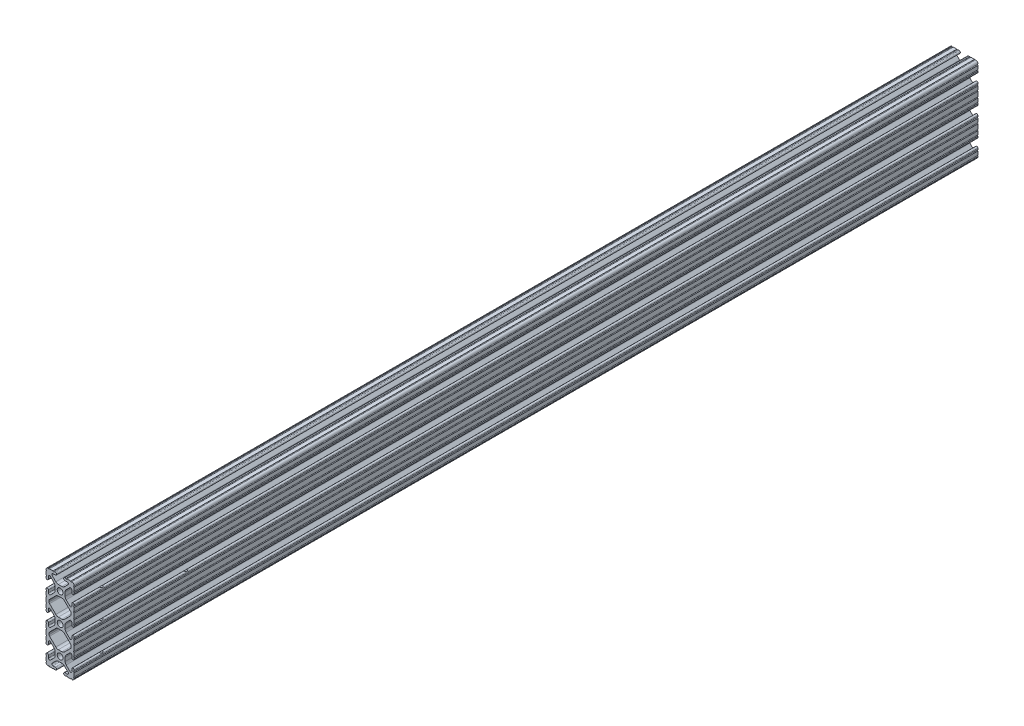
SolidWorks part; units mm, degrees
ref_plane "Front" through (0, 0, 0) normal (0, 0, 1) x (1, 0, 0)
ref_plane "Top" through (0, 0, 0) normal (0, 1, 0) x (1, 0, 0)
ref_plane "Right" through (0, 0, 0) normal (1, 0, 0) x (0, 0, -1)
sketch "Sketch1" plane through (0, 0, 0) normal (0, 0, 1) x (1, 0, 0)
  line L0 (-7.4908, -34.8742) -> (7.4908, -34.8742) construction
  line L1 (-3.1974, -36.9951) -> (3.1974, -36.9951) construction
  line L2 (-7.4908, 34.8742) -> (7.4908, 34.8742) construction
  line L3 (-3.1974, 36.9951) -> (3.1974, 36.9951) construction
  line L16 (-9.9314, -12.1463) -> (-9.9314, -13.2537)
  line L17 (-3.8759, -5.4384) -> (-9.4702, -11.0327)
  line L18 (1.6308, -4.5085) -> (-1.6308, -4.5085)
  line L19 (9.4702, -11.0327) -> (3.8759, -5.4384)
  line L20 (9.9314, -13.2537) -> (9.9314, -12.1463)
  line L21 (3.8759, -19.9616) -> (9.4702, -14.3673)
  line L22 (-1.6308, -20.8915) -> (1.6308, -20.8915)
  line L23 (-9.4702, -14.3673) -> (-3.8759, -19.9616)
  line L32 (-9.9314, 13.2537) -> (-9.9314, 12.1463)
  line L33 (-3.8759, 19.9616) -> (-9.4702, 14.3673)
  line L34 (1.6308, 20.8915) -> (-1.6308, 20.8915)
  line L35 (9.4702, 14.3673) -> (3.8759, 19.9616)
  line L36 (9.9314, 12.1463) -> (9.9314, 13.2537)
  line L37 (3.8759, 5.4384) -> (9.4702, 11.0327)
  line L38 (-1.6308, 4.5085) -> (1.6308, 4.5085)
  line L39 (-9.4702, 11.0327) -> (-3.8759, 5.4384)
  line L152 (-12.7, 34.9504) -> (-12.7, 31.7246)
  line L153 (-12.7, 30.7086) -> (-12.7, 29.7023)
  line L154 (-10.4902, 29.7023) -> (-10.4902, 31.8748)
  line L155 (-8.7558, 32.5932) -> (-5.4384, 29.2759)
  line L156 (-4.5085, 27.0308) -> (-4.5085, 23.7692)
  line L157 (-5.4384, 21.5241) -> (-8.7558, 18.2068)
  line L158 (-10.4902, 18.9252) -> (-10.4902, 21.0977)
  line L159 (-12.7, 21.0977) -> (-12.7, 20.0914)
  line L160 (-12.7, 19.0754) -> (-12.7, 15.8496)
  line L161 (-12.7, 14.8336) -> (-12.7, 10.5664)
  line L162 (-12.7, 9.5504) -> (-12.7, 6.3246)
  line L163 (-12.7, 5.3086) -> (-12.7, 4.3023)
  line L164 (-10.4902, 4.3023) -> (-10.4902, 6.4748)
  line L165 (-8.7558, 7.1932) -> (-5.4384, 3.8759)
  line L166 (-4.5085, 1.6308) -> (-4.5085, -1.6308)
  line L167 (-5.4384, -3.8759) -> (-8.7558, -7.1932)
  line L168 (-10.4902, -6.4748) -> (-10.4902, -4.3023)
  line L169 (-12.7, -4.3023) -> (-12.7, -5.3086)
  line L170 (-12.7, -6.3246) -> (-12.7, -9.5504)
  line L171 (-12.7, -10.5664) -> (-12.7, -14.8336)
  line L172 (-12.7, -15.8496) -> (-12.7, -19.0754)
  line L173 (-12.7, -20.0914) -> (-12.7, -21.0977)
  line L174 (-10.4902, -21.0977) -> (-10.4902, -18.9252)
  line L175 (-8.7558, -18.2068) -> (-5.4384, -21.5241)
  line L176 (-4.5085, -23.7692) -> (-4.5085, -27.0308)
  line L177 (-5.4384, -29.2759) -> (-8.7558, -32.5932)
  line L178 (-10.4902, -31.8748) -> (-10.4902, -29.7023)
  line L179 (-12.7, -29.7023) -> (-12.7, -30.7086)
  line L180 (-12.7, -31.7246) -> (-12.7, -34.9504)
  line L181 (-9.5504, -38.1) -> (-6.3246, -38.1)
  line L182 (-5.3086, -38.1) -> (-4.3023, -38.1)
  line L183 (-4.3023, -35.8902) -> (-6.4748, -35.8902)
  line L184 (-7.1932, -34.1558) -> (-3.8759, -30.8384)
  line L185 (-1.6308, -29.9085) -> (1.6308, -29.9085)
  line L186 (3.8759, -30.8384) -> (7.1932, -34.1558)
  line L187 (6.4748, -35.8902) -> (4.3023, -35.8902)
  line L188 (4.3023, -38.1) -> (5.3086, -38.1)
  line L189 (6.3246, -38.1) -> (9.5504, -38.1)
  line L190 (12.7, -34.9504) -> (12.7, -31.7246)
  line L191 (12.7, -30.7086) -> (12.7, -29.7023)
  line L192 (10.4902, -29.7023) -> (10.4902, -31.8748)
  line L193 (8.7558, -32.5932) -> (5.4384, -29.2759)
  line L194 (4.5085, -27.0308) -> (4.5085, -23.7692)
  line L195 (5.4384, -21.5241) -> (8.7558, -18.2068)
  line L196 (10.4902, -18.9252) -> (10.4902, -21.0977)
  line L197 (12.7, -21.0977) -> (12.7, -20.0914)
  line L198 (12.7, -19.0754) -> (12.7, -15.8496)
  line L199 (12.7, -14.8336) -> (12.7, -10.5664)
  line L200 (12.7, -9.5504) -> (12.7, -6.3246)
  line L201 (12.7, -5.3086) -> (12.7, -4.3023)
  line L202 (10.4902, -4.3023) -> (10.4902, -6.4748)
  line L203 (8.7558, -7.1932) -> (5.4384, -3.8759)
  line L204 (4.5085, -1.6308) -> (4.5085, 1.6308)
  line L205 (5.4384, 3.8759) -> (8.7558, 7.1932)
  line L206 (10.4902, 6.4748) -> (10.4902, 4.3023)
  line L207 (12.7, 4.3023) -> (12.7, 5.3086)
  line L208 (12.7, 6.3246) -> (12.7, 9.5504)
  line L209 (12.7, 10.5664) -> (12.7, 14.8336)
  line L210 (12.7, 15.8496) -> (12.7, 19.0754)
  line L211 (12.7, 20.0914) -> (12.7, 21.0977)
  line L212 (10.4902, 21.0977) -> (10.4902, 18.9252)
  line L213 (8.7558, 18.2068) -> (5.4384, 21.5241)
  line L214 (4.5085, 23.7692) -> (4.5085, 27.0308)
  line L215 (5.4384, 29.2759) -> (8.7558, 32.5932)
  line L216 (10.4902, 31.8748) -> (10.4902, 29.7023)
  line L217 (12.7, 29.7023) -> (12.7, 30.7086)
  line L218 (12.7, 31.7246) -> (12.7, 34.9504)
  line L219 (9.5504, 38.1) -> (6.3246, 38.1)
  line L220 (5.3086, 38.1) -> (4.3023, 38.1)
  line L221 (4.3023, 35.8902) -> (6.4748, 35.8902)
  line L222 (7.1932, 34.1558) -> (3.8759, 30.8384)
  line L223 (1.6308, 29.9085) -> (-1.6308, 29.9085)
  line L224 (-3.8759, 30.8384) -> (-7.1932, 34.1558)
  line L225 (-6.4748, 35.8902) -> (-4.3023, 35.8902)
  line L226 (-4.3023, 38.1) -> (-5.3086, 38.1)
  line L227 (-6.3246, 38.1) -> (-9.5504, 38.1)
  circle A2 centre (0, -25.4) radius 2.6035
  circle A4 centre (0, 0) radius 2.6035
  circle A6 centre (0, 25.4) radius 2.6035
  arc A18 (-9.9314, -13.2537) -> (-9.4702, -14.3673) centre (-8.3566, -13.2537) ccw
  arc A19 (-9.4702, -11.0327) -> (-9.9314, -12.1463) centre (-8.3566, -12.1463) ccw
  arc A20 (-1.6308, -4.5085) -> (-3.8759, -5.4384) centre (-1.6308, -7.6835) ccw
  arc A21 (3.8759, -5.4384) -> (1.6308, -4.5085) centre (1.6308, -7.6835) ccw
  arc A22 (9.9314, -12.1463) -> (9.4702, -11.0327) centre (8.3566, -12.1463) ccw
  arc A23 (9.4702, -14.3673) -> (9.9314, -13.2537) centre (8.3566, -13.2537) ccw
  arc A24 (1.6308, -20.8915) -> (3.8759, -19.9616) centre (1.6308, -17.7165) ccw
  arc A25 (-3.8759, -19.9616) -> (-1.6308, -20.8915) centre (-1.6308, -17.7165) ccw
  arc A36 (-9.9314, 12.1463) -> (-9.4702, 11.0327) centre (-8.3566, 12.1463) ccw
  arc A37 (-9.4702, 14.3673) -> (-9.9314, 13.2537) centre (-8.3566, 13.2537) ccw
  arc A38 (-1.6308, 20.8915) -> (-3.8759, 19.9616) centre (-1.6308, 17.7165) ccw
  arc A39 (3.8759, 19.9616) -> (1.6308, 20.8915) centre (1.6308, 17.7165) ccw
  arc A40 (9.9314, 13.2537) -> (9.4702, 14.3673) centre (8.3566, 13.2537) ccw
  arc A41 (9.4702, 11.0327) -> (9.9314, 12.1463) centre (8.3566, 12.1463) ccw
  arc A42 (1.6308, 4.5085) -> (3.8759, 5.4384) centre (1.6308, 7.6835) ccw
  arc A43 (-3.8759, 5.4384) -> (-1.6308, 4.5085) centre (-1.6308, 7.6835) ccw
  arc A168 (-10.5664, 38.1) -> (-12.7, 35.9664) centre (-10.592, 35.992) ccw
  arc A169 (-12.7, 34.9504) -> (-12.7, 35.9664) centre (-12.7, 35.4584) ccw
  arc A170 (-12.7, 30.7086) -> (-12.7, 31.7246) centre (-12.7, 31.2166) ccw
  arc A171 (-12.7, 29.7023) -> (-10.4902, 29.7023) centre (-11.5951, 29.7023) ccw
  arc A172 (-8.7558, 32.5932) -> (-10.4902, 31.8748) centre (-9.4742, 31.8748) ccw
  arc A173 (-4.5085, 27.0308) -> (-5.4384, 29.2759) centre (-7.6835, 27.0308) ccw
  arc A174 (-5.4384, 21.5241) -> (-4.5085, 23.7692) centre (-7.6835, 23.7692) ccw
  arc A175 (-10.4902, 18.9252) -> (-8.7558, 18.2068) centre (-9.4742, 18.9252) ccw
  arc A176 (-10.4902, 21.0977) -> (-12.7, 21.0977) centre (-11.5951, 21.0977) ccw
  arc A177 (-12.7, 19.0754) -> (-12.7, 20.0914) centre (-12.7, 19.5834) ccw
  arc A178 (-12.7, 14.8336) -> (-12.7, 15.8496) centre (-12.7, 15.3416) ccw
  arc A179 (-12.7, 9.5504) -> (-12.7, 10.5664) centre (-12.7, 10.0584) ccw
  arc A180 (-12.7, 5.3086) -> (-12.7, 6.3246) centre (-12.7, 5.8166) ccw
  arc A181 (-12.7, 4.3023) -> (-10.4902, 4.3023) centre (-11.5951, 4.3023) ccw
  arc A182 (-8.7558, 7.1932) -> (-10.4902, 6.4748) centre (-9.4742, 6.4748) ccw
  arc A183 (-4.5085, 1.6308) -> (-5.4384, 3.8759) centre (-7.6835, 1.6308) ccw
  arc A184 (-5.4384, -3.8759) -> (-4.5085, -1.6308) centre (-7.6835, -1.6308) ccw
  arc A185 (-10.4902, -6.4748) -> (-8.7558, -7.1932) centre (-9.4742, -6.4748) ccw
  arc A186 (-10.4902, -4.3023) -> (-12.7, -4.3023) centre (-11.5951, -4.3023) ccw
  arc A187 (-12.7, -6.3246) -> (-12.7, -5.3086) centre (-12.7, -5.8166) ccw
  arc A188 (-12.7, -10.5664) -> (-12.7, -9.5504) centre (-12.7, -10.0584) ccw
  arc A189 (-12.7, -15.8496) -> (-12.7, -14.8336) centre (-12.7, -15.3416) ccw
  arc A190 (-12.7, -20.0914) -> (-12.7, -19.0754) centre (-12.7, -19.5834) ccw
  arc A191 (-12.7, -21.0977) -> (-10.4902, -21.0977) centre (-11.5951, -21.0977) ccw
  arc A192 (-8.7558, -18.2068) -> (-10.4902, -18.9252) centre (-9.4742, -18.9252) ccw
  arc A193 (-4.5085, -23.7692) -> (-5.4384, -21.5241) centre (-7.6835, -23.7692) ccw
  arc A194 (-5.4384, -29.2759) -> (-4.5085, -27.0308) centre (-7.6835, -27.0308) ccw
  arc A195 (-10.4902, -31.8748) -> (-8.7558, -32.5932) centre (-9.4742, -31.8748) ccw
  arc A196 (-10.4902, -29.7023) -> (-12.7, -29.7023) centre (-11.5951, -29.7023) ccw
  arc A197 (-12.7, -31.7246) -> (-12.7, -30.7086) centre (-12.7, -31.2166) ccw
  arc A198 (-12.7, -35.9664) -> (-12.7, -34.9504) centre (-12.7, -35.4584) ccw
  arc A199 (-12.7, -35.9664) -> (-10.5664, -38.1) centre (-10.592, -35.992) ccw
  arc A200 (-9.5504, -38.1) -> (-10.5664, -38.1) centre (-10.0584, -38.1) ccw
  arc A201 (-5.3086, -38.1) -> (-6.3246, -38.1) centre (-5.8166, -38.1) ccw
  arc A202 (-4.3023, -38.1) -> (-4.3023, -35.8902) centre (-4.3023, -36.9951) ccw
  arc A203 (-7.1932, -34.1558) -> (-6.4748, -35.8902) centre (-6.4748, -34.8742) ccw
  arc A204 (-1.6308, -29.9085) -> (-3.8759, -30.8384) centre (-1.6308, -33.0835) ccw
  arc A205 (3.8759, -30.8384) -> (1.6308, -29.9085) centre (1.6308, -33.0835) ccw
  arc A206 (6.4748, -35.8902) -> (7.1932, -34.1558) centre (6.4748, -34.8742) ccw
  arc A207 (4.3023, -35.8902) -> (4.3023, -38.1) centre (4.3023, -36.9951) ccw
  arc A208 (6.3246, -38.1) -> (5.3086, -38.1) centre (5.8166, -38.1) ccw
  arc A209 (10.5664, -38.1) -> (9.5504, -38.1) centre (10.0584, -38.1) ccw
  arc A210 (10.5664, -38.1) -> (12.7, -35.9664) centre (10.592, -35.992) ccw
  arc A211 (12.7, -34.9504) -> (12.7, -35.9664) centre (12.7, -35.4584) ccw
  arc A212 (12.7, -30.7086) -> (12.7, -31.7246) centre (12.7, -31.2166) ccw
  arc A213 (12.7, -29.7023) -> (10.4902, -29.7023) centre (11.5951, -29.7023) ccw
  arc A214 (8.7558, -32.5932) -> (10.4902, -31.8748) centre (9.4742, -31.8748) ccw
  arc A215 (4.5085, -27.0308) -> (5.4384, -29.2759) centre (7.6835, -27.0308) ccw
  arc A216 (5.4384, -21.5241) -> (4.5085, -23.7692) centre (7.6835, -23.7692) ccw
  arc A217 (10.4902, -18.9252) -> (8.7558, -18.2068) centre (9.4742, -18.9252) ccw
  arc A218 (10.4902, -21.0977) -> (12.7, -21.0977) centre (11.5951, -21.0977) ccw
  arc A219 (12.7, -19.0754) -> (12.7, -20.0914) centre (12.7, -19.5834) ccw
  arc A220 (12.7, -14.8336) -> (12.7, -15.8496) centre (12.7, -15.3416) ccw
  arc A221 (12.7, -9.5504) -> (12.7, -10.5664) centre (12.7, -10.0584) ccw
  arc A222 (12.7, -5.3086) -> (12.7, -6.3246) centre (12.7, -5.8166) ccw
  arc A223 (12.7, -4.3023) -> (10.4902, -4.3023) centre (11.5951, -4.3023) ccw
  arc A224 (8.7558, -7.1932) -> (10.4902, -6.4748) centre (9.4742, -6.4748) ccw
  arc A225 (4.5085, -1.6308) -> (5.4384, -3.8759) centre (7.6835, -1.6308) ccw
  arc A226 (5.4384, 3.8759) -> (4.5085, 1.6308) centre (7.6835, 1.6308) ccw
  arc A227 (10.4902, 6.4748) -> (8.7558, 7.1932) centre (9.4742, 6.4748) ccw
  arc A228 (10.4902, 4.3023) -> (12.7, 4.3023) centre (11.5951, 4.3023) ccw
  arc A229 (12.7, 6.3246) -> (12.7, 5.3086) centre (12.7, 5.8166) ccw
  arc A230 (12.7, 10.5664) -> (12.7, 9.5504) centre (12.7, 10.0584) ccw
  arc A231 (12.7, 15.8496) -> (12.7, 14.8336) centre (12.7, 15.3416) ccw
  arc A232 (12.7, 20.0914) -> (12.7, 19.0754) centre (12.7, 19.5834) ccw
  arc A233 (12.7, 21.0977) -> (10.4902, 21.0977) centre (11.5951, 21.0977) ccw
  arc A234 (8.7558, 18.2068) -> (10.4902, 18.9252) centre (9.4742, 18.9252) ccw
  arc A235 (4.5085, 23.7692) -> (5.4384, 21.5241) centre (7.6835, 23.7692) ccw
  arc A236 (5.4384, 29.2759) -> (4.5085, 27.0308) centre (7.6835, 27.0308) ccw
  arc A237 (10.4902, 31.8748) -> (8.7558, 32.5932) centre (9.4742, 31.8748) ccw
  arc A238 (10.4902, 29.7023) -> (12.7, 29.7023) centre (11.5951, 29.7023) ccw
  arc A239 (12.7, 31.7246) -> (12.7, 30.7086) centre (12.7, 31.2166) ccw
  arc A240 (12.7, 35.9664) -> (12.7, 34.9504) centre (12.7, 35.4584) ccw
  arc A241 (12.7, 35.9664) -> (10.5664, 38.1) centre (10.592, 35.992) ccw
  arc A242 (9.5504, 38.1) -> (10.5664, 38.1) centre (10.0584, 38.1) ccw
  arc A243 (5.3086, 38.1) -> (6.3246, 38.1) centre (5.8166, 38.1) ccw
  arc A244 (4.3023, 38.1) -> (4.3023, 35.8902) centre (4.3023, 36.9951) ccw
  arc A245 (7.1932, 34.1558) -> (6.4748, 35.8902) centre (6.4748, 34.8742) ccw
  arc A246 (1.6308, 29.9085) -> (3.8759, 30.8384) centre (1.6308, 33.0835) ccw
  arc A247 (-3.8759, 30.8384) -> (-1.6308, 29.9085) centre (-1.6308, 33.0835) ccw
  arc A248 (-6.4748, 35.8902) -> (-7.1932, 34.1558) centre (-6.4748, 34.8742) ccw
  arc A249 (-4.3023, 35.8902) -> (-4.3023, 38.1) centre (-4.3023, 36.9951) ccw
  arc A250 (-6.3246, 38.1) -> (-5.3086, 38.1) centre (-5.8166, 38.1) ccw
  arc A251 (-10.5664, 38.1) -> (-9.5504, 38.1) centre (-10.0584, 38.1) ccw
extrude "Boss-Extrude1" add sketch "Sketch1" along normal mid plane 812.8
sketch "Sketch2" plane through (4.5085, 0, 0) normal (1, 0, 0) x (0, 0, -1)
  line L0 (-406.4, 38.1) -> (406.4, 38.1) construction
  line L1 (-406.4, 23.7692) -> (-406.4, 27.0308) construction
  line L2 (-406.4, -1.6308) -> (-406.4, 1.6308) construction
  line L3 (-406.4, -27.0308) -> (-406.4, -23.7692) construction
  circle A0 centre (-381, 25.4) radius 3.5
  circle A1 centre (-381, 0) radius 3.5
  circle A2 centre (-381, -25.4) radius 3.5
  dimension "D1" = 7
  dimension "D2" = 12.7
  dimension "D3" = 25.4
  dimension "D4" = 7
  dimension "D5" = 7
  dimension "D6" = 25.4
  dimension "D7" = 25.4
  dimension "D8" = 25.4
  dimension "D9" = 25.4
extrude "Cut-Extrude1" cut sketch "Sketch2" against normal through all both and the other way through all
sketch "Sketch3" plane through (4.5085, 0, 0) normal (1, 0, 0) x (0, 0, -1)
  line L1 (-406.4, -1.6308) -> (-406.4, 1.6308) construction
  line L2 (-406.4, 38.1) -> (406.4, 38.1) construction
  circle A0 centre (-304.8, 0) radius 3.5
  dimension "D1" = 7
  dimension "D2" = 101.6
  dimension "D3" = 38.1
extrude "Cut-Extrude2" cut sketch "Sketch3" against normal through all both and the other way through all
